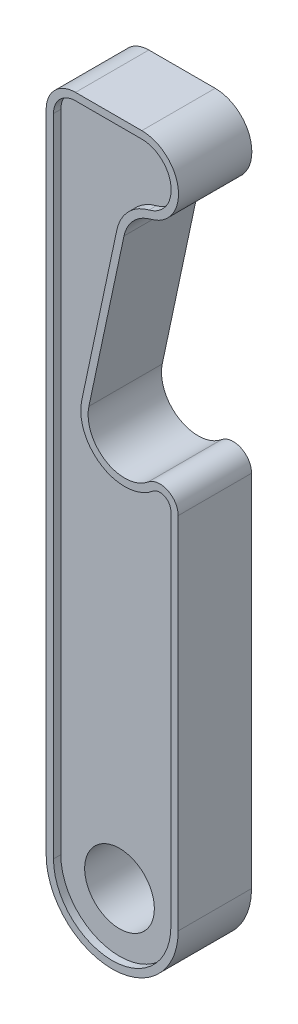
SolidWorks part; units mm, degrees
ref_plane "Front Plane" through (0, 0, 0) normal (1, 0, 0) x (0, 1, 0)
ref_plane "Top Plane" through (0, 0, 0) normal (0, 0, 1) x (0, 1, 0)
ref_plane "Right Plane" through (0, 0, 0) normal (0, 1, 0) x (-1, 0, 0)
sketch "Sketch2" plane through (0, 0, 0) normal (0, 0, 1) x (0, 1, 0)
  line L0 (0, 9) -> (88, 9)
  line L1 (0, -9) -> (49.0303, -9)
  line L2 (92, 5) -> (92, -4.0386)
  line L3 (55.8472, 3.1733) -> (78.3472, -1.6093)
  line L4 (0, 8) -> (88, 8)
  line L5 (91, 5) -> (91, -4.0386)
  line L6 (56.0551, 4.1514) -> (78.5551, -0.6311)
  line L7 (0, -8) -> (49.0303, -8)
  circle A0 centre (0, 0) radius 4.75
  arc A1 (0, 9) -> (0, -9) centre (0, 0) ccw
  arc A2 (88, 9) -> (92, 5) centre (88, 5) cw
  arc A3 (49.0303, -9) -> (50.9561, -4.9058) centre (49.0303, -6.5) ccw
  arc A4 (50.9561, -4.9058) -> (55.8472, 3.1733) centre (54.8077, -1.7175) cw
  arc A5 (78.3472, -1.6093) -> (82.1538, -5.2693) centre (77.3077, -6.5) cw
  arc A6 (82.1538, -5.2693) -> (92, -4.0386) centre (87, -4.0386) ccw
  arc A7 (88, 8) -> (91, 5) centre (88, 5) cw
  arc A8 (83.1231, -5.0232) -> (91, -4.0386) centre (87, -4.0386) ccw
  arc A9 (78.5551, -0.6311) -> (83.1231, -5.0232) centre (77.3077, -6.5) cw
  arc A10 (50.1858, -5.5435) -> (56.0551, 4.1514) centre (54.8077, -1.7175) cw
  arc A11 (49.0303, -8) -> (50.1858, -5.5435) centre (49.0303, -6.5) ccw
  arc A12 (0, 8) -> (0, -8) centre (0, 0) ccw
  point P19 (-9, 0)
  point P20 (87.6201, -9)
  dimension "D1" = 18
  dimension "D2" = 9.5
  dimension "D3" = 4
  dimension "D5" = 2.5
  dimension "D6" = 5
  dimension "D7" = 5
  dimension "D8" = 5
  dimension "D4" = 12
  dimension "D9" = 22.5
  dimension "D10" = 101
  dimension "D11" = 1
extrude "Boss-Extrude2" add sketch "Sketch2" along normal mid plane 9 contours L4 A12 L7 A11 A10 L6 A9 A8 L5 A7 A0 region at (-0.8524, 38.4445, 0)
extrude "Boss-Extrude3" add sketch "Sketch2<4>" along normal blind 10 from surface contours A5 A6 L2 A2 L0 A1 L1 A3 A4 L3 A12 L4 A7 L5 A8 A9 L6 A10 A11 L7 region at (-8.8974, 44, 0) starting at face at (4.75, 0, -4.5)
sketch "Sketch2<4>" plane through (0, 0, 0) normal (0, 0, 1) x (0, 1, 0) same geometry as "Sketch2"
